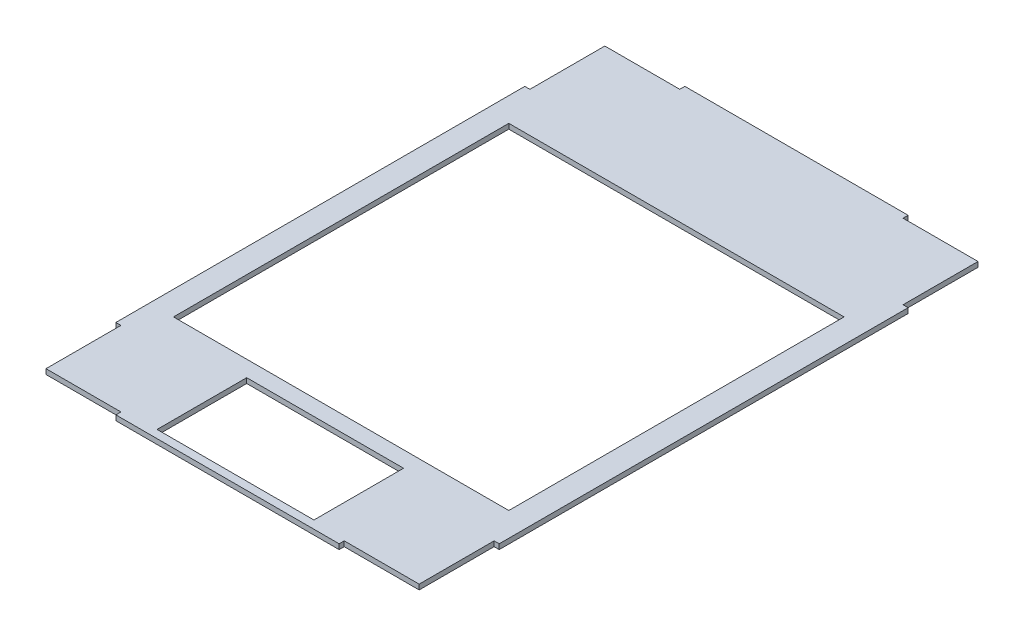
SolidWorks part; units mm, degrees
ref_plane "Front Plane" through (0, 0, 0) normal (0, 0, 1) x (1, 0, 0)
ref_plane "Top Plane" through (0, 0, 0) normal (0, 1, 0) x (1, 0, 0)
ref_plane "Right Plane" through (0, 0, 0) normal (1, 0, 0) x (0, 0, -1)
sketch "Sketch1" plane through (0, 0, 0) normal (0, 1, 0) x (1, 0, 0)
  line L1 (-209.5, -209.5) -> (209.5, -209.5)
  line L2 (-209.5, -209.5) -> (-209.5, 209.5)
  line L3 (-209.5, 209.5) -> (209.5, 209.5)
  line L4 (209.5, -209.5) -> (209.5, 209.5)
  line L5 (-209.5, -209.5) -> (209.5, 209.5) construction
  line L6 (-209.5, 209.5) -> (209.5, -209.5) construction
  line L7 (-239.5, -351.5) -> (239.5, -351.5)
  line L8 (-239.5, -351.5) -> (-239.5, 359.5)
  line L9 (-239.5, 359.5) -> (239.5, 359.5)
  line L10 (239.5, -351.5) -> (239.5, 359.5)
  line L11 (-98, -341.5) -> (98, -341.5)
  line L12 (-98, -341.5) -> (-98, -229.5)
  line L13 (-98, -229.5) -> (98, -229.5)
  line L14 (98, -341.5) -> (98, -229.5)
  line L15 (-98, -341.5) -> (98, -229.5) construction
  line L16 (-98, -229.5) -> (98, -341.5) construction
  point P0 (0, 0)
  point P6 (0, 0)
  point P11 (0, -351.5)
  point P12 (0, -285.5)
  point P17 (0, 0)
  dimension "D1" = 419
  dimension "D2" = 30
  dimension "D3" = 10
  dimension "D4" = 150
  dimension "D5" = 196
  dimension "D6" = 112
  dimension "D7" = 20
extrude "Boss-Extrude1" add sketch "Sketch1" along normal mid plane 6.35
sketch "Sketch2" plane through (0, 3.175, 0) normal (0, 1, 0) x (1, 0, 0)
  line L0 (-239.5, 359.5) -> (-239.5, 259.5)
  line L1 (-239.5, 359.5) -> (-239.5, -351.5) construction
  line L2 (-239.5, 259.5) -> (-233.15, 259.5)
  line L3 (-233.15, 259.5) -> (-233.15, 353.15)
  line L4 (-233.15, 353.15) -> (-139.5, 353.15)
  line L5 (-139.5, 353.15) -> (-139.5, 359.5)
  line L6 (239.5, 359.5) -> (-239.5, 359.5) construction
  line L7 (-139.5, 359.5) -> (-239.5, 359.5)
  line L8 (239.5, 359.5) -> (139.5, 359.5)
  line L9 (139.5, 359.5) -> (139.5, 353.15)
  line L10 (139.5, 353.15) -> (233.15, 353.15)
  line L11 (233.15, 353.15) -> (233.15, 259.5)
  line L12 (233.15, 259.5) -> (239.5, 259.5)
  line L13 (239.5, -351.5) -> (239.5, 359.5) construction
  line L14 (239.5, 259.5) -> (239.5, 359.5)
  line L15 (239.5, -351.5) -> (239.5, -251.5)
  line L16 (239.5, -251.5) -> (233.15, -251.5)
  line L17 (233.15, -251.5) -> (233.15, -345.15)
  line L18 (233.15, -345.15) -> (139.5, -345.15)
  line L19 (139.5, -345.15) -> (139.5, -351.5)
  line L20 (-239.5, -351.5) -> (239.5, -351.5) construction
  line L21 (139.5, -351.5) -> (239.5, -351.5)
  line L22 (-239.5, -351.5) -> (-139.5, -351.5)
  line L23 (-139.5, -351.5) -> (-139.5, -345.15)
  line L24 (-139.5, -345.15) -> (-233.15, -345.15)
  line L25 (-233.15, -345.15) -> (-233.15, -251.5)
  line L26 (-233.15, -251.5) -> (-239.5, -251.5)
  line L27 (-239.5, -251.5) -> (-239.5, -351.5)
  dimension "D1" = 100
  dimension "D2" = 6.35
extrude "Cut-Extrude1" cut sketch "Sketch2" against normal through all
